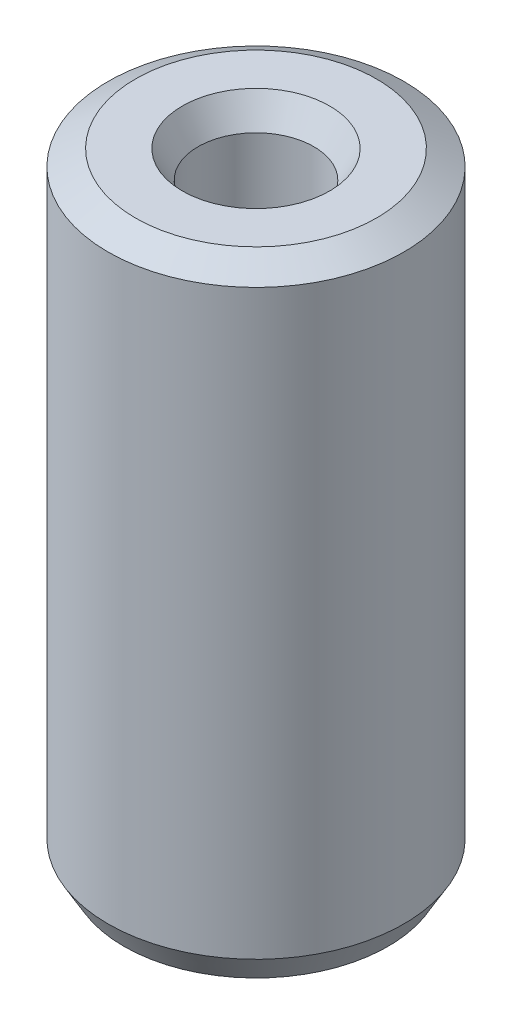
SolidWorks part; units mm, degrees
ref_plane "Front Plane" through (0, 0, 0) normal (0, 0, 1) x (1, 0, 0)
ref_plane "Top Plane" through (0, 0, 0) normal (0, 1, 0) x (1, 0, 0)
ref_plane "Right Plane" through (0, 0, 0) normal (1, 0, 0) x (0, 0, -1)
sketch "Sketch1" plane through (0, 0, 0) normal (0, 1, 0) x (1, 0, 0)
  circle A0 centre (0, 0) radius 35
  dimension "SLEEVE_OD" = 70
extrude "Boss-Extrude1" add sketch "Sketch1" along normal blind 147.943
sketch "Sketch2" plane through (0, 0, 0) normal (0, 1, 0) x (1, 0, 0)
  circle A0 centre (0, 0) radius 13.7021
  dimension "BORE_D" = 27.4042
extrude "Cut-Extrude1" cut sketch "Sketch2" along normal through all
chamfer "Chamfer1" distance 3.737 angle 60 4 edges at (0, 147.943, 13.7021) (0, 0, 13.7021) (0, 0, 35) (0, 147.943, 35) first distance on face at (0, 147.943, 13.7021) first distance on face at (0, 0, 13.7021) first distance on face at (0, 147.943, 35)
